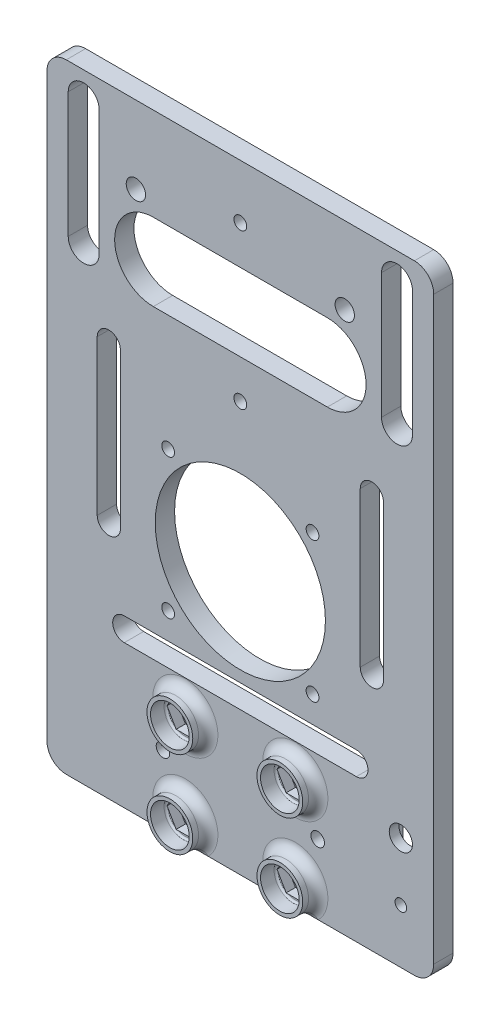
SolidWorks part; units mm, degrees
ref_plane "Front Plane" through (0, 0, 0) normal (0, 0, 1) x (1, 0, 0)
ref_plane "Top Plane" through (0, 0, 0) normal (0, 1, 0) x (1, 0, 0)
ref_plane "Right Plane" through (0, 0, 0) normal (1, 0, 0) x (0, 0, -1)
sketch "Sketch1" plane through (0, 0, 0) normal (0, 0, 1) x (1, 0, 0)
  line L0 (0, 80) -> (0, -80) construction
  line L1 (-50, -80) -> (50, -80)
  line L2 (-50, -80) -> (-50, 80)
  line L3 (-50, 80) -> (50, 80)
  line L4 (50, -80) -> (50, 80)
  line L5 (-50, -80) -> (50, 80) construction
  line L6 (-50, 80) -> (50, -80) construction
  line L7 (-50, 16) -> (50, 16) construction
  line L9 (-14.2186, -74) -> (14.2186, -74) construction
  line L10 (-14.2186, -74) -> (-14.2186, -51.6) construction
  line L11 (-14.2186, -51.6) -> (14.2186, -51.6) construction
  line L12 (14.2186, -74) -> (14.2186, -51.6) construction
  line L13 (-14.2186, -74) -> (14.2186, -51.6) construction
  line L14 (-14.2186, -51.6) -> (14.2186, -74) construction
  line L15 (-18.6652, -30.2) -> (18.6652, -30.2) construction
  line L16 (-18.6652, -30.2) -> (-18.6652, 6) construction
  line L17 (-18.6652, 6) -> (18.6652, 6) construction
  line L18 (18.6652, -30.2) -> (18.6652, 6) construction
  line L19 (-18.6652, -30.2) -> (18.6652, 6) construction
  line L20 (-18.6652, 6) -> (18.6652, -30.2) construction
  circle A0 centre (0, 66) radius 1.65
  circle A1 centre (0, 26) radius 1.65
  circle A2 centre (14.2186, -51.6) radius 2.75
  circle A3 centre (-14.2186, -51.6) radius 2.75
  circle A4 centre (-14.2186, -74) radius 2.75
  circle A5 centre (14.2186, -74) radius 2.75
  circle A6 centre (-18.6652, 6) radius 1.65
  circle A7 centre (18.6652, 6) radius 1.65
  circle A8 centre (18.6652, -30.2) radius 1.65
  circle A9 centre (-18.6652, -30.2) radius 1.65
  point P0 (0, 0)
  point P14 (0, -62.8)
  point P23 (0, -12.1)
  dimension "D3" = 3.3
  dimension "D5" = 3.3
  dimension "D10" = 5.5
  dimension "D11" = 5.5
  dimension "D12" = 5.5
  dimension "D13" = 5.5
  dimension "D17" = 3.3
  dimension "D18" = 3.3
  dimension "D19" = 3.3
  dimension "D20" = 3.3
  dimension "D1" = 160
  dimension "D2" = 100
  dimension "D4" = 14
  dimension "D6" = 40
  dimension "D7" = 64
  dimension "D8" = 36.2
  dimension "D9" = 6
  dimension "D14" = 22.4
  dimension "D15" = 52
  dimension "D16" = 36.2
  dimension "D21" = 10
extrude "Boss-Extrude1" add sketch "Sketch1" along normal blind 5
sketch "Sketch3" plane through (0, 0, 5) normal (0, 0, 1) x (1, 0, 0)
  line L0 (-34, 22) -> (-34, -18) construction
  line L1 (-31, 22) -> (-31, -18)
  line L2 (-37, 22) -> (-37, -18)
  line L3 (-50, 16) -> (50, 16) construction
  line L4 (0, 80) -> (0, -80) construction
  line L5 (0, 0) -> (0, -80) construction
  line L6 (34, 22) -> (34, -18) construction
  line L7 (31, 22) -> (31, -18)
  line L8 (37, 22) -> (37, -18)
  line L9 (-22.5, 46) -> (22.5, 46) construction
  line L10 (-22.5, 56) -> (22.5, 56)
  line L11 (-22.5, 36) -> (22.5, 36)
  line L12 (-50, 80) -> (50, 80) construction
  line L13 (-30, -40) -> (30, -40) construction
  line L14 (-30, -37) -> (30, -37)
  line L15 (-30, -43) -> (30, -43)
  line L16 (-50, -80) -> (50, -80) construction
  arc A0 (-31, 22) -> (-37, 22) centre (-34, 22) ccw
  arc A1 (-37, -18) -> (-31, -18) centre (-34, -18) ccw
  arc A2 (31, 22) -> (37, 22) centre (34, 22) cw
  arc A3 (37, -18) -> (31, -18) centre (34, -18) cw
  arc A4 (-22.5, 56) -> (-22.5, 36) centre (-22.5, 46) ccw
  arc A5 (22.5, 36) -> (22.5, 56) centre (22.5, 46) ccw
  arc A6 (-30, -37) -> (-30, -43) centre (-30, -40) ccw
  arc A7 (30, -43) -> (30, -37) centre (30, -40) ccw
  point P2 (-34, 2)
  point P16 (34, 2)
  point P23 (0, 46)
  point P29 (0, -40)
  dimension "D10" = 60
  dimension "D1" = 6
  dimension "D2" = 40
  dimension "D3" = 6
  dimension "D4" = 34
  dimension "D5" = 45
  dimension "D6" = 34
  dimension "D7" = 20
  dimension "D8" = 40
  dimension "D9" = 6
extrude "Cut-Extrude1" cut sketch "Sketch3" against normal through all
sketch "Sketch5" plane through (0, 0, 5) normal (0, 0, 1) x (1, 0, 0)
  line L0 (-18.6652, 6) -> (18.6652, -30.2) construction
  line L1 (0, -2.75) -> (0, 2.75) construction
  line L2 (-50, 10) -> (-31, 10) construction
  line L3 (-50, 10) -> (-50, 80) construction
  line L4 (-50, 80) -> (-31, 80) construction
  line L5 (-31, 10) -> (-31, 80) construction
  line L6 (-50, 10) -> (-31, 80) construction
  line L7 (-50, 80) -> (-31, 10) construction
  line L8 (50, 80) -> (-50, 80) construction
  line L9 (-50, 38.5) -> (-31, 38.5)
  line L10 (22.5, 56) -> (-22.5, 56) construction
  line L11 (-40.5, 40.7037) -> (-40.5, 73.0955) construction
  line L12 (-44.5, 40.7037) -> (-44.5, 73.0955)
  line L13 (-36.5, 40.7037) -> (-36.5, 73.0955)
  line L14 (40.5, 40.7037) -> (40.5, 73.0955) construction
  line L15 (44.5, 40.7037) -> (44.5, 73.0955)
  line L16 (36.5, 40.7037) -> (36.5, 73.0955)
  line L17 (0, -12.1) -> (0, -77) construction
  line L18 (-27.5, -77) -> (27.5, -77) construction
  line L19 (-27.5, -77) -> (-27.5, -47) construction
  line L20 (-27.5, -47) -> (27.5, -47) construction
  line L21 (27.5, -77) -> (27.5, -47) construction
  line L22 (-27.5, -77) -> (27.5, -47) construction
  line L23 (-27.5, -47) -> (27.5, -77) construction
  line L24 (-30, -43) -> (30, -43) construction
  circle A0 centre (0, -12.1) radius 22
  circle A1 centre (-27, 60) radius 2.5
  arc A2 (-44.5, 40.7037) -> (-36.5, 40.7037) centre (-40.5, 40.7037) ccw
  arc A3 (-36.5, 73.0955) -> (-44.5, 73.0955) centre (-40.5, 73.0955) ccw
  arc A4 (44.5, 40.7037) -> (36.5, 40.7037) centre (40.5, 40.7037) cw
  arc A5 (36.5, 73.0955) -> (44.5, 73.0955) centre (40.5, 73.0955) cw
  circle A6 centre (27, 60) radius 2.5
  point P6 (-40.5, 45)
  point P21 (-40.5, 56.8996)
  point P26 (0, -62)
  point P34 (40.5, 56.8996)
  point P42 (0, 0)
  dimension "D1" = 44
  dimension "D7" = 5
  dimension "D2" = 19
  dimension "D3" = 70
  dimension "D4" = 40.5
  dimension "D5" = 35
  dimension "D6" = 41.5
  dimension "D8" = 4
  dimension "D9" = 4
  dimension "D10" = 8
  dimension "D11" = 32.3917
  dimension "D12" = 30
  dimension "D13" = 55
  dimension "D14" = 4
extrude "Cut-Extrude2" cut sketch "Sketch5" against normal through all contours A0 | L13 A3 L12 A2 L9 | A1 | A6 | A5 L16 A4 L15 | L9 A2 region at (-40.5, 57.4362, 5) region at (-40.5, 37.7656, 5) region at (40.5, 56.8996, 5) region at (0, -12.1, 5) region at (-27, 60, 5) region at (27, 60, 5)
fillet "Fillet1" radius 5 4 edges at (50, -80, 2.5) (-50, -80, 2.5) (50, 80, 2.5) (-50, 80, 2.5)
sketch "Sketch6" plane through (0, 0, 0) normal (0, 0, -1) x (-1, 0, 0)
  line L0 (-41.5, -51) -> (-41.5, -69.7746) construction
  line L1 (30, -43) -> (-30, -43) construction
  line L2 (-27.5, -77) -> (-27.5, -47) construction
  circle A0 centre (-41.5, -51) radius 3
  circle A1 centre (-41.5, -66) radius 1.5
  dimension "D1" = 6
  dimension "D2" = 3
  dimension "D3" = 15
  dimension "D4" = 8
  dimension "D5" = 14
extrude "Cut-Extrude3" cut sketch "Sketch6" against normal through all
sketch "Sketch7" plane through (0, 0, 0) normal (0, 0, -1) x (-1, 0, 0)
  line L1 (-46, -59.15) -> (-37, -59.15)
  line L2 (-46, -59.15) -> (-46, -42.85)
  line L3 (-46, -42.85) -> (-37, -42.85)
  line L4 (-37, -59.15) -> (-37, -42.85)
  line L5 (-46, -59.15) -> (-37, -42.85) construction
  line L6 (-46, -42.85) -> (-37, -59.15) construction
  point P0 (-41.5, -51)
  dimension "D1" = 9
  dimension "D2" = 16.3
extrude "Cut-Extrude4" cut sketch "Sketch7" against normal blind 2.5
sketch "Sketch8" plane through (0, 0, 5) normal (0, 0, 1) x (1, 0, 0)
  line L1 (-11.8479, -47.5021) -> (-16.5822, -47.4979)
  line L2 (-16.5822, -47.4979) -> (-18.9529, -51.5959)
  line L3 (-18.9529, -51.5959) -> (-16.5894, -55.6979)
  line L4 (-16.5894, -55.6979) -> (-11.8551, -55.7021)
  line L5 (-11.8551, -55.7021) -> (-9.4844, -51.6041)
  line L6 (-9.4844, -51.6041) -> (-11.8479, -47.5021)
  line L7 (18.9529, -74) -> (16.5858, -69.9)
  line L8 (16.5858, -69.9) -> (11.8515, -69.9)
  line L9 (11.8515, -69.9) -> (9.4844, -74)
  line L10 (9.4844, -74) -> (11.8515, -78.1)
  line L11 (11.8515, -78.1) -> (16.5858, -78.1)
  line L12 (16.5858, -78.1) -> (18.9529, -74)
  line L13 (-9.4844, -74) -> (-11.8515, -69.9)
  line L14 (-11.8515, -69.9) -> (-16.5858, -69.9)
  line L15 (-16.5858, -69.9) -> (-18.9529, -74)
  line L16 (-18.9529, -74) -> (-16.5858, -78.1)
  line L17 (-16.5858, -78.1) -> (-11.8515, -78.1)
  line L18 (-11.8515, -78.1) -> (-9.4844, -74)
  line L19 (18.9529, -51.6) -> (16.5858, -47.5)
  line L20 (16.5858, -47.5) -> (11.8515, -47.5)
  line L21 (11.8515, -47.5) -> (9.4844, -51.6)
  line L22 (9.4844, -51.6) -> (11.8515, -55.7)
  line L23 (11.8515, -55.7) -> (16.5858, -55.7)
  line L24 (16.5858, -55.7) -> (18.9529, -51.6)
  circle A0 centre (-14.2186, -51.6) radius 4.1 construction
  circle A1 centre (14.2186, -74) radius 4.1 construction
  circle A2 centre (-14.2186, -74) radius 4.1 construction
  circle A3 centre (14.2186, -51.6) radius 4.1 construction
  point P28 (0, 0)
  dimension "D1" = 8.2
  dimension "D2" = 8.2
  dimension "D3" = 8.2
  dimension "D4" = 8.2
extrude "Cut-Extrude5" cut sketch "Sketch8" against normal blind 2.4
sketch "Sketch9" plane through (0, 0, 5) normal (0, 0, 1) x (1, 0, 0)
  circle A1 centre (-14.2186, -51.6) radius 5
  circle A2 centre (14.2186, -51.6) radius 5
  circle A4 centre (-14.2186, -74) radius 5
  circle A5 centre (14.2186, -74) radius 5
  circle A6 centre (-14.2186, -51.6) radius 5.92
  circle A7 centre (-14.2186, -74) radius 5.92
  circle A8 centre (14.2186, -51.6) radius 5.92
  circle A9 centre (14.2186, -74) radius 5.92
  dimension "D1" = 10
  dimension "D2" = 10
  dimension "D3" = 10
  dimension "D4" = 10
  dimension "D5" = 0.92
extrude "Boss-Extrude2" add sketch "Sketch9" along normal blind 4
fillet "Fillet2" radius 2.5 4 edges at (-20.1386, -74, 5) (8.2986, -74, 5) (8.2986, -51.6, 5) (-20.1386, -51.6, 5)
sketch "Sketch10" plane through (0, 0, 5) normal (0, 0, 1) x (1, 0, 0)
  line L0 (-20, -62) -> (20, -62)
  circle A0 centre (-20, -62) radius 1.75
  circle A1 centre (20, -62) radius 1.75
  point P4 (0, -62)
  dimension "D2" = 3.5
  dimension "D3" = 3.5
  dimension "D1" = 40
extrude "Cut-Extrude6" cut sketch "Sketch10" against normal through all contours A0 | A1 region at (20, -60.2995, 5) region at (-21.7005, -62, 5)
fillet "Fillet4" radius 0.5 4 edges at (19.2186, -74, 5) (19.2186, -51.6, 5) (-9.2186, -51.6, 5) (-9.2186, -74, 5)
sketch "Sketch11" plane through (0, 0, 0) normal (0, 0, -1) x (-1, 0, 0)
  line L1 (-16.8534, -62) -> (-18.4267, -59.275)
  line L2 (-18.4267, -59.275) -> (-21.5733, -59.275)
  line L3 (-21.5733, -59.275) -> (-23.1466, -62)
  line L4 (-23.1466, -62) -> (-21.5733, -64.725)
  line L5 (-21.5733, -64.725) -> (-18.4267, -64.725)
  line L6 (-18.4267, -64.725) -> (-16.8534, -62)
  line L7 (21.6208, -59.303) -> (18.4748, -59.2478)
  line L8 (18.4748, -59.2478) -> (16.8539, -61.9448)
  line L9 (16.8539, -61.9448) -> (18.3792, -64.697)
  line L10 (18.3792, -64.697) -> (21.5252, -64.7522)
  line L11 (21.5252, -64.7522) -> (23.1461, -62.0552)
  line L12 (23.1461, -62.0552) -> (21.6208, -59.303)
  circle A0 centre (-20, -62) radius 2.725 construction
  circle A1 centre (20, -62) radius 2.725 construction
  dimension "D1" = 5.45
  dimension "D2" = 5.45
extrude "Cut-Extrude7" cut sketch "Sketch11" against normal blind 2.5
